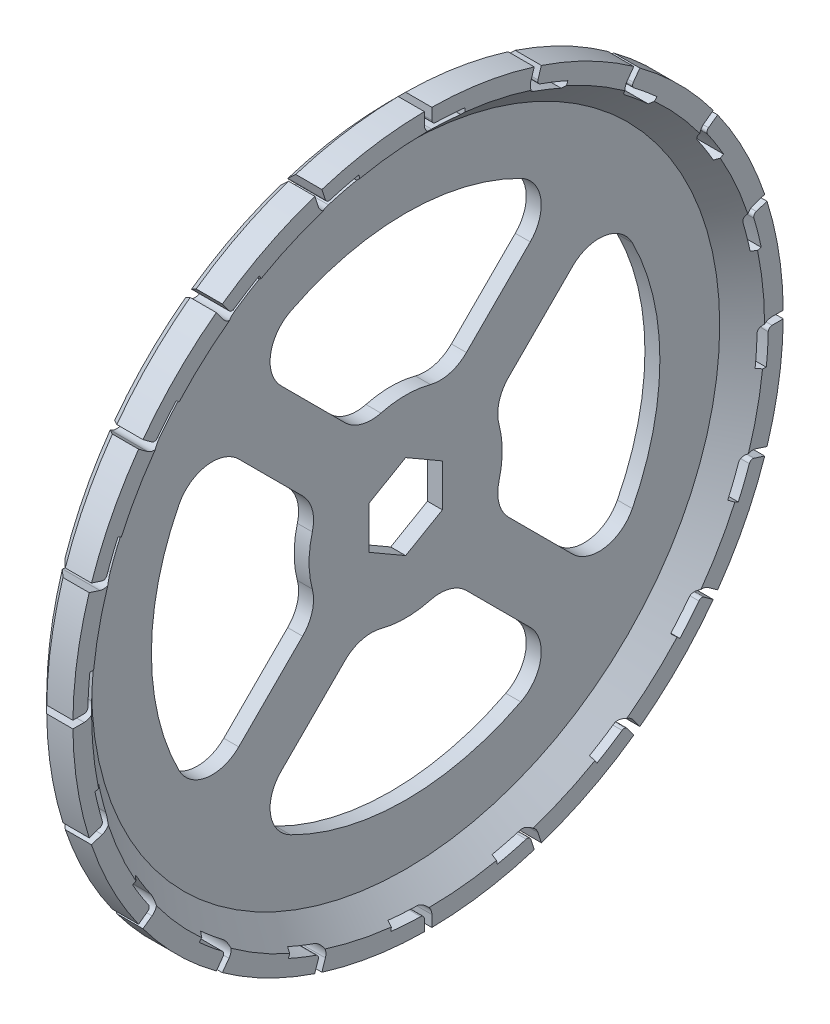
SolidWorks part; units mm, degrees
note: The reader was unsure of these and kept them because the rebuilt part matched: shared geometry of "Sketch1<4>".
ref_plane "Front Plane" through (0, 0, 0) normal (0, 0, 1) x (1, 0, 0)
ref_plane "Top Plane" through (0, 0, 0) normal (0, 1, 0) x (1, 0, 0)
ref_plane "Right Plane" through (0, 0, 0) normal (1, 0, 0) x (0, 0, -1)
sketch "Sketch1" plane through (0, 0, 0) normal (1, 0, 0) x (0, 0, -1)
  line L1 (0, 5.6725) -> (-4.9125, 2.8362)
  line L2 (-4.9125, 2.8362) -> (-4.9125, -2.8362)
  line L3 (-4.9125, -2.8362) -> (0, -5.6725)
  line L4 (0, -5.6725) -> (4.9125, -2.8362)
  line L5 (4.9125, -2.8362) -> (4.9125, 2.8362)
  line L6 (4.9125, 2.8362) -> (0, 5.6725)
  line L7 (0.5, 47.5) -> (0.5, 45.9891)
  line L8 (-0.5, 47.5) -> (-0.5, 45.9891)
  line L9 (4.9671, 45.2281) -> (4.8579, 44.234)
  circle A0 centre (0, 0) radius 4.9125 construction
  arc A1 (-0.5, 47.4974) -> (0.5, 47.4974) centre (0, 0) ccw
  arc A3 (4.9671, 45.2281) -> (0.9891, 45.4892) centre (0, 0) ccw
  arc A4 (4.8579, 44.234) -> (0.9674, 44.4895) centre (0, 0) ccw
  arc A5 (0.9674, 44.4895) -> (-0.5, 45.9891) centre (1, 45.9891) cw
  arc A6 (0.9891, 45.4892) -> (0.5, 45.9891) centre (1, 45.9891) cw
  circle A7 centre (0, 0) radius 47.5026
  dimension "D1" = 95
  dimension "D3" = 0.5
  dimension "D2" = 1.5
extrude "Boss-Extrude1" add sketch "Sketch1" along normal blind 2 contours A6 A3 L9 A4 A5 L8 A1 L7 L6 L5 L4 L3 L2 L1 | L7 A7 L8 A5 A4 L9 A3 A6
sketch "Sketch2" plane through (2, 0, 0) normal (1, 0, 0) x (0, 0, -1)
  circle A0 centre (0, 0) radius 45
  line M1 (-0.5, 47.5) -> (-0.5, 47.4974)
  arc M2 (-0.5, 47.4974) -> (0.5, 47.4974) centre (0, 0) ccw
  line M3 (0.5, 47.4974) -> (0.5, 47.5)
  arc M4 (0.5, 47.5) -> (-0.5, 47.5) centre (0, 0) ccw
  dimension "D1" = 90
extrude "Boss-Extrude2" add sketch "Sketch2" along normal blind 3 contours A0 M4 M1 M2 M3
chamfer "Chamfer1" distance 3 angle 45 1 edges at (2, 0, -45)
chamfer "Chamfer2" distance 1.5 angle 45 1 edges at (0, -47.5, 0)
extrude "Cut-Extrude2" cut sketch "Sketch1<4>" along normal through all contours L7 A7 L8 A5 A4 L9 A3 A6
sketch "Sketch1<4>" plane through (0, 0, 0) normal (1, 0, 0) x (0, 0, -1) same geometry as "Sketch1"
pattern_circular "CirPattern1" count 20 over 360 about axis through (0, 0, 0) along (1, 0, 0) of "Cut-Extrude2"
sketch "Sketch4" plane through (2, 0, 0) normal (1, 0, 0) x (0, 0, -1)
  line L0 (0, 0) -> (-3.4737, 3.4737)
  line L1 (0, 0) -> (-3.4737, -3.4737)
  line L2 (0, 0) -> (3.4737, -3.4737)
  line L3 (0, 0) -> (3.4737, 3.4737)
  line L4 (-9.1305, 9.1305) -> (-24.0416, 24.0416)
  line L5 (-9.1305, -9.1305) -> (-24.0416, -24.0416)
  line L6 (9.1305, -9.1305) -> (24.0416, -24.0416)
  line L7 (9.1305, 9.1305) -> (24.0416, 24.0416)
  line L8 (-6.3021, 11.9589) -> (-21.2132, 26.8701)
  line L9 (-11.9589, -6.3021) -> (-26.8701, -21.2132)
  line L10 (6.3021, -11.9589) -> (21.2132, -26.8701)
  line L11 (11.9589, 6.3021) -> (26.8701, 21.2132)
  line L12 (-11.9589, 6.3021) -> (-26.8701, 21.2132)
  line L13 (-6.3021, -11.9589) -> (-21.2132, -26.8701)
  line L14 (11.9589, -6.3021) -> (26.8701, -21.2132)
  line L15 (6.3021, 11.9589) -> (21.2132, 26.8701)
  line L16 (-11.9589, -6.3021) -> (-9.542, -3.8851)
  line L17 (-6.3021, -11.9589) -> (-3.4737, -9.1305)
  line L18 (-11.9589, 6.3021) -> (-10.4215, 4.7647)
  line L19 (-6.3021, 11.9589) -> (-3.815, 9.4719)
  line L20 (6.3021, 11.9589) -> (3.815, 9.4719)
  line L21 (11.9589, 6.3021) -> (10.0836, 4.4267)
  line L22 (11.9589, -6.3021) -> (10.4161, -4.7593)
  line L23 (6.3021, -11.9589) -> (4.4394, -10.0962)
  circle A1 centre (0, 0) radius 4.9125
  circle A2 centre (0, 0) radius 34
  circle A3 centre (0, 0) radius 34
  circle A4 centre (0, 0) radius 12.9125
  dimension "D2" = 8
  dimension "D3" = 4
  dimension "D1" = 8
  dimension "D4" = 4
extrude "Cut-Extrude3" cut sketch "Sketch4" against normal blind 3 contours A4 L18 L12 A3 L9 L16 | A4 L20 L15 A3 L8 L19 | A4 L22 L14 A3 L11 L21 | A4 L17 L13 A3 L10 L23
fillet "Fillet1" radius 5 16 edges at (1, -5.853, 11.5098) (1, 5.853, 11.5098) (1, -21.0462, 26.7031) (1, 21.0462, 26.7031) (1, 26.7031, -21.0462) (1, 26.7031, 21.0462) (1, 11.5098, -5.853) (1, 11.5098, 5.853) (1, -21.0462, -26.7031) (1, 21.0462, -26.7031) (1, 5.853, -11.5098) (1, -5.853, -11.5098) (1, -26.7031, -21.0462) (1, -26.7031, 21.0462) (1, -11.5098, 5.853) (1, -11.5098, -5.853)
